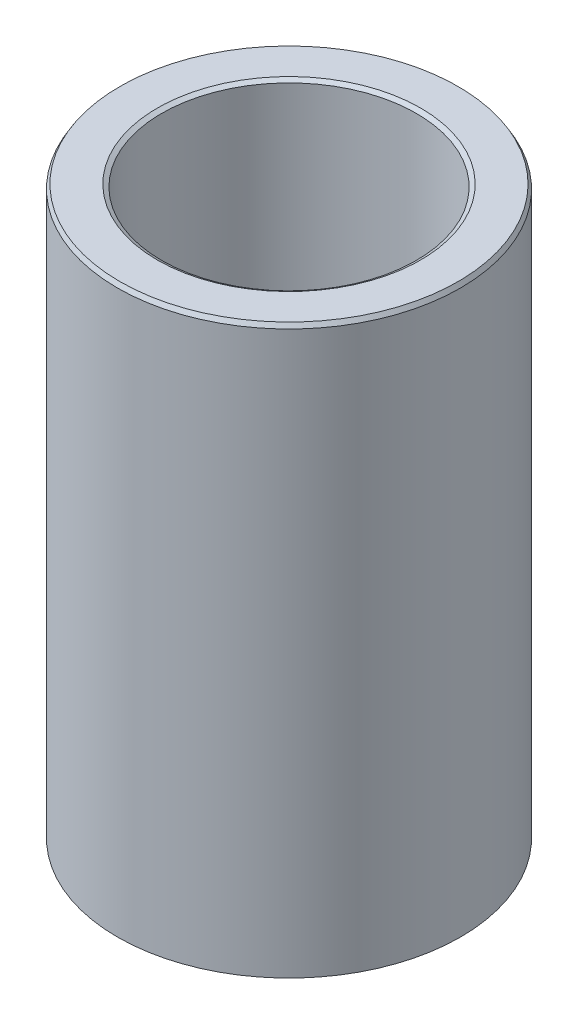
SolidWorks part; units mm, degrees
ref_plane "Front Plane" through (0, 0, 0) normal (0, 0, 1) x (1, 0, 0)
ref_plane "Top Plane" through (0, 0, 0) normal (0, 1, 0) x (1, 0, 0)
ref_plane "Right Plane" through (0, 0, 0) normal (1, 0, 0) x (0, 0, -1)
sketch "Sketch1" plane through (0, 0, 0) normal (0, 1, 0) x (1, 0, 0)
  circle A0 centre (0, 0) radius 30
  dimension "SLEEVE_OD" = 60
extrude "Boss-Extrude1" add sketch "Sketch1" along normal blind 99.4927
sketch "Sketch2" plane through (0, 0, 0) normal (0, 1, 0) x (1, 0, 0)
  circle A0 centre (0, 0) radius 22.2755
  dimension "BORE_D" = 44.5509
extrude "Cut-Extrude1" cut sketch "Sketch2" along normal through all
chamfer "Chamfer1" distance 0.7503 angle 30 4 edges at (0, 99.4927, 22.2755) (0, 0, 22.2755) (0, 0, 30) (0, 99.4927, 30) first distance on face at (0, 99.4927, 22.2755) first distance on face at (0, 0, 22.2755) first distance on face at (0, 99.4927, 30)
